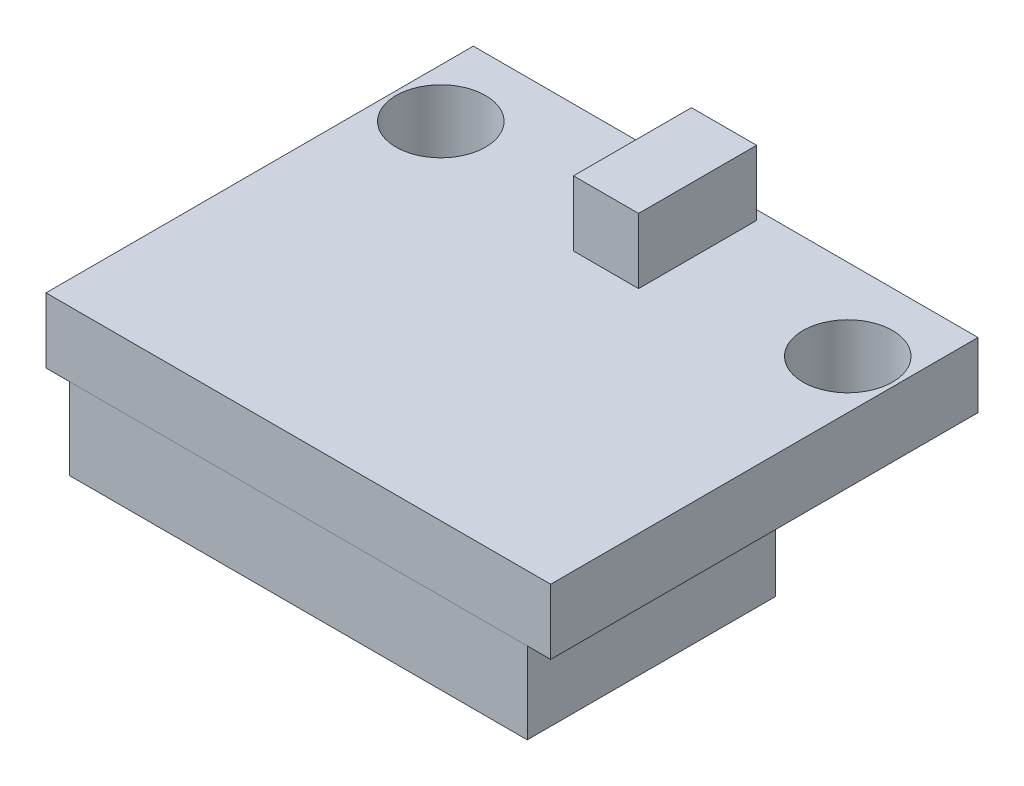
SolidWorks part; units mm, degrees
ref_plane "Front Plane" through (0, 0, 0) normal (0, 0, 1) x (1, 0, 0)
ref_plane "Top Plane" through (0, 0, 0) normal (0, 1, 0) x (1, 0, 0)
ref_plane "Right Plane" through (0, 0, 0) normal (1, 0, 0) x (0, 0, -1)
ref_axis "X Axis" through (-88.99, 0, 0) along (1, 0, 0)
ref_axis "Y Axis" through (0, 55, 0) along (0, -1, 0)
ref_axis "Z Axis" through (0, 0, -88.99) along (0, 0, 1)
sketch "Sketch1" plane through (0, 0, 0) normal (0, 1, 0) x (1, 0, 0)
  line L0 (-6.39, 0) -> (6.01, 0) construction
  line L2 (0, 1.68) -> (0, -8.82) construction
  line L3 (-6.39, 1.68) -> (6.01, 1.68)
  line L4 (-6.39, 1.68) -> (-6.39, -8.82)
  line L5 (-6.39, -8.82) -> (6.01, -8.82)
  line L6 (6.01, 1.68) -> (6.01, -8.82)
  dimension "D1" = 10.5
  dimension "D2" = 12.4
  dimension "D3" = 6.01
  dimension "D4" = 1.68
extrude "Boss-Extrude1" add sketch "Sketch1" along normal blind 1.6
sketch "Sketch2" plane through (0, 0, 0) normal (0, 1, 0) x (1, 0, 0)
  line L0 (-0.19, 1.68) -> (-0.19, -8.82) construction
  line L1 (6.01, 1.68) -> (-6.39, 1.68) construction
  line L2 (-6.39, -8.82) -> (6.01, -8.82) construction
  line L3 (6.01, -8.82) -> (6.01, 1.68) construction
  circle A0 centre (4.81, -0.32) radius 1.1
  circle A1 centre (-5.19, -0.32) radius 1.1
  dimension "D1" = 2.2
  dimension "D2" = 1.2
  dimension "D3" = 2
extrude "Cut-Extrude1" cut sketch "Sketch2" along normal through all
sketch "Sketch3" plane through (0, 1.6, 0) normal (0, 1, 0) x (1, 0, 0)
  line L1 (-0.8, -1.45) -> (0.8, -1.45)
  line L2 (-0.8, -1.45) -> (-0.8, 1.45)
  line L3 (-0.8, 1.45) -> (0.8, 1.45)
  line L4 (0.8, -1.45) -> (0.8, 1.45)
  line L5 (-0.8, -1.45) -> (0.8, 1.45) construction
  line L6 (-0.8, 1.45) -> (0.8, -1.45) construction
  point P0 (0, 0)
  dimension "D1" = 2.9
  dimension "D2" = 1.6
extrude "Boss-Extrude2" add sketch "Sketch3" along normal blind 1.6 separate body
sketch "Sketch4" plane through (0, 0, 0) normal (0, -1, 0) x (1, 0, 0)
  line L0 (-6.39, 8.82) -> (6.01, 8.82) construction
  line L1 (-5.815, 8.82) -> (5.435, 8.82)
  line L2 (-5.815, 8.82) -> (-5.815, 2.72)
  line L3 (-5.815, 2.72) -> (5.435, 2.72)
  line L4 (5.435, 8.82) -> (5.435, 2.72)
  line L5 (-0.19, 8.82) -> (-0.19, -1.68) construction
  line L6 (6.01, -1.68) -> (-6.39, -1.68) construction
  dimension "D1" = 11.25
  dimension "D2" = 6.1
extrude "Boss-Extrude3" add sketch "Sketch4" along normal blind 2 separate body
